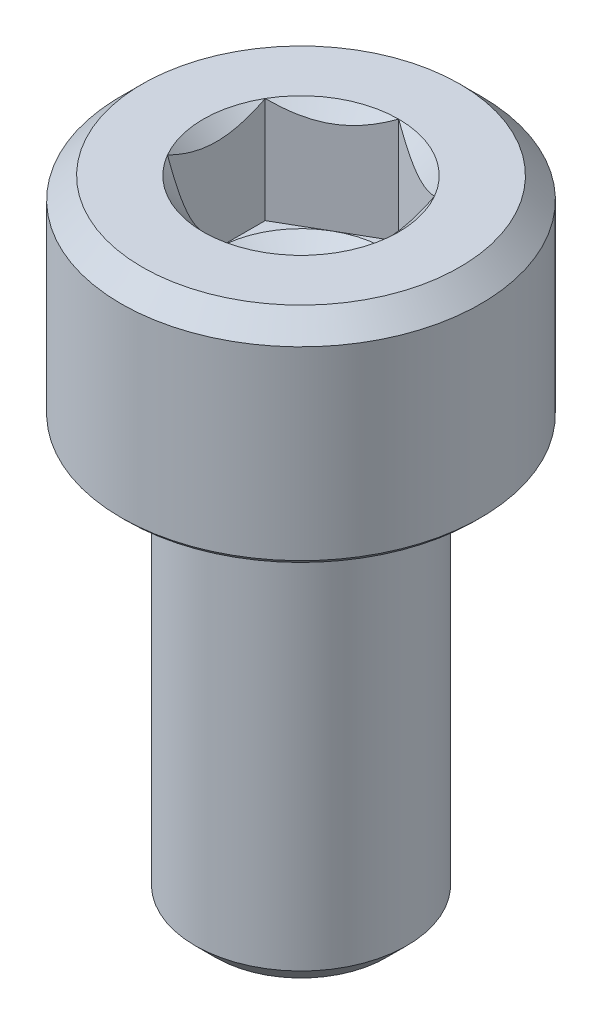
SolidWorks part; units mm, degrees
ref_plane "Front Plane" through (0, 0, 0) normal (0, 0, 1) x (1, 0, 0)
ref_plane "Top Plane" through (0, 0, 0) normal (0, 1, 0) x (1, 0, 0)
ref_plane "Right Plane" through (0, 0, 0) normal (1, 0, 0) x (0, 0, -1)
sketch "Sketch1" plane through (0, 0, 0) normal (0, 0, 1) x (1, 0, 0)
  line L0 (0, 1.3453) -> (2, 2.5)
  line L1 (2, 2.5) -> (2, 4.6906)
  line L2 (2, 4.6906) -> (2.3094, 5)
  line L3 (2.3094, 5) -> (3.75, 5)
  line L4 (3.75, 5) -> (4.25, 4.5)
  line L5 (4.25, 4.5) -> (4.25, 0.125)
  line L6 (4.25, 0.125) -> (4.125, 0)
  line L7 (4.125, 0) -> (2.55, 0)
  line L8 (2.55, 0) -> (2.5, -0.6)
  line L9 (2.5, -0.6) -> (2.5, -9.5095)
  line L10 (2.5, -9.5095) -> (2.0095, -10)
  line L11 (2.0095, -10) -> (0, -10)
  line L12 (0, -10) -> (0, 1.3453)
  line L13 (0, -10) -> (0, 5) construction
revolve "Revolve1" add sketch "Sketch1" angle 360 about L13 reverse direction yes
cosmetic thread "Cosmetic Thread1" parameters "D1"=7.6, "D2"=4.019
ref_plane "Plane1" through (0, 5, 0) normal (0, 1, 0) x (1, 0, 0)
sketch "Sketch2" plane through (0, 5, 0) normal (0, 1, 0) x (1, 0, 0)
  line L0 (-2, -1.1547) -> (0, -2.3094)
  line L1 (0, -2.3094) -> (2, -1.1547)
  line L2 (2, -1.1547) -> (2, 1.1547)
  line L3 (2, 1.1547) -> (0, 2.3094)
  line L4 (0, 2.3094) -> (-2, 1.1547)
  line L5 (-2, 1.1547) -> (-2, -1.1547)
extrude "Cut-Extrude1" cut sketch "Sketch2" against normal blind 2.5
ref_plane "Plane2" through (0, -10, 0) normal (0, 1, 0) x (1, 0, 0)
ref_plane "ANBAU XY" through (0, 0, 0) normal (0, 1, 0) x (1, 0, 0)
ref_plane "ANBAU XZ" through (0, 0, 0) normal (0, 0, 1) x (1, 0, 0)
ref_plane "ANBAU YZ" through (0, 0, 0) normal (1, 0, 0) x (0, 0, -1)
ref_axis "ANBAU X" through (-80.9, 0, 0) along (1, 0, 0)
ref_axis "ANBAU Y" through (0, 0, 50) along (0, 0, -1)
ref_axis "ANBAU Z" through (0, 50, 0) along (0, -1, 0)
sketch3d "ANBAU"
  point P0 (0, 0, 0)
ref_plane "Schraube XY" through (0, 0, 0) normal (0, 1, 0) x (1, 0, 0)
ref_plane "Schraube XZ" through (0, 0, 0) normal (0, 0, 1) x (1, 0, 0)
ref_plane "Schraube YZ" through (0, 0, 0) normal (1, 0, 0) x (0, 0, -1)
ref_axis "Schraube X" through (-80.9, 0, 0) along (1, 0, 0)
ref_axis "Schraube Y" through (0, 0, 50) along (0, 0, -1)
ref_axis "Schraube Z" through (0, 50, 0) along (0, -1, 0)
sketch3d "Schraube"
  point P0 (0, 0, 0)
ref_plane "insert XY" through (0, 0, 0) normal (0, 1, 0) x (1, 0, 0)
ref_plane "insert XZ" through (0, 0, 0) normal (0, 0, 1) x (1, 0, 0)
ref_plane "insert YZ" through (0, 0, 0) normal (1, 0, 0) x (0, 0, -1)
ref_axis "insert X" through (-80.9, 0, 0) along (1, 0, 0)
ref_axis "insert Y" through (0, 0, 50) along (0, 0, -1)
ref_axis "insert Z" through (0, 50, 0) along (0, -1, 0)
sketch3d "insert"
  point P0 (0, 0, 0)
ref_plane "schrauben_punkt XY" through (0, -10, 0) normal (0, 1, 0) x (1, 0, 0)
ref_plane "schrauben_punkt XZ" through (0, 0, 0) normal (0, 0, 1) x (1, 0, 0)
ref_plane "schrauben_punkt YZ" through (0, 0, 0) normal (1, 0, 0) x (0, 0, -1)
ref_axis "schrauben_punkt X" through (-80.9, -10, 0) along (1, 0, 0)
ref_axis "schrauben_punkt Y" through (0, -10, 50) along (0, 0, -1)
ref_axis "schrauben_punkt Z" through (0, 50, 0) along (0, -1, 0)
sketch3d "schrauben_punkt"
  point P0 (0, -10, 0)
other "Freeze***"
